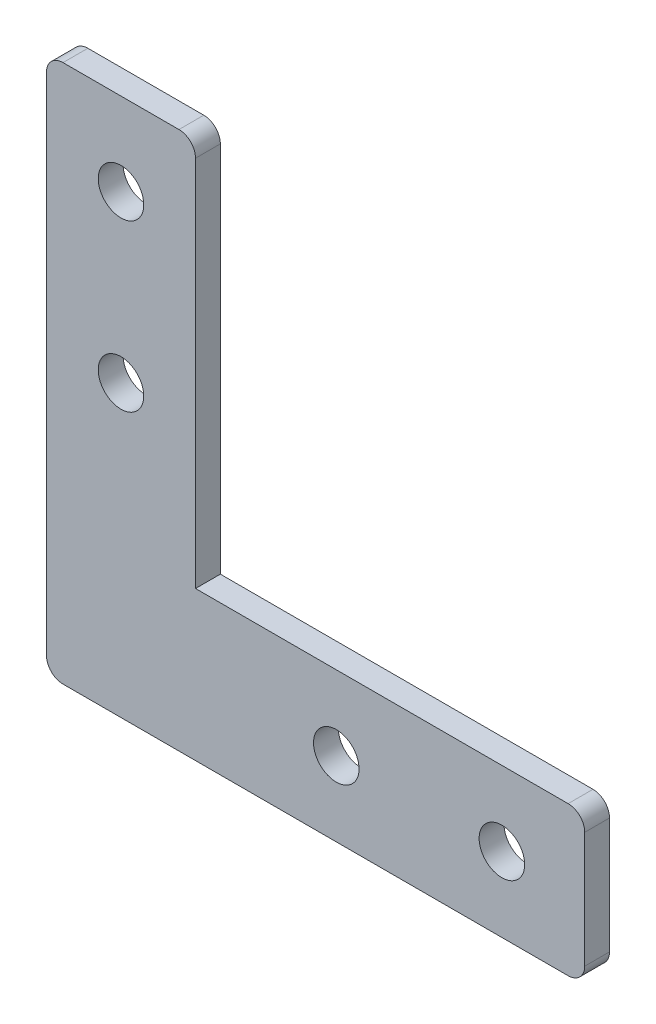
SolidWorks part; units mm, degrees
material "1023 Kohlenstoffstahlblech (SS)"
ref_plane "Ebene vorne" through (0, 0, 0) normal (0, 0, 1) x (1, 0, 0)
ref_plane "Ebene oben" through (0, 0, 0) normal (0, 1, 0) x (1, 0, 0)
ref_plane "Ebene rechts" through (0, 0, 0) normal (1, 0, 0) x (0, 0, -1)
sketch "Skizze1" plane through (0, 0, 0) normal (0, 0, 1) x (1, 0, 0)
  line L0 (0, 0) -> (0, 47)
  line L1 (0, 47) -> (-18, 47)
  line L2 (-18, 47) -> (-18, -18)
  line L3 (-18, -18) -> (47, -18)
  line L4 (47, -18) -> (47, 0)
  line L5 (47, 0) -> (0, 0)
  dimension "D1" = 18
  dimension "D2" = 65
extrude "Aufsatz-Linear austragen1" add sketch "Skizze1" along normal blind 3
hole_wizard "Durchgangsloch für M51" positions "Skizze2" profile "Skizze3" hole size "M5" standard "DIN" end condition through all
sketch "Skizze2" plane through (0, 0, 3) normal (0, 0, 1) x (1, 0, 0)
  line L0 (-9, 47) -> (-9, 37) construction
  line L1 (0, 47) -> (-18, 47) construction
  line L2 (-9, 37) -> (-9, 17) construction
  line L3 (-9, 17) -> (-9, -18) construction
  line L4 (-18, -18) -> (47, -18) construction
  line L7 (47, -9) -> (37, -9) construction
  line L8 (47, -18) -> (47, 0) construction
  line L9 (37, -9) -> (17, -9) construction
  line L10 (17, -9) -> (-18, -9) construction
  line L11 (-18, 47) -> (-18, -18) construction
  point P1 (-9, 37)
  point P4 (-9, 17)
  point P13 (37, -9)
  point P17 (17, -9)
  dimension "D1" = 35
  dimension "D2" = 20
sketch "Skizze3" plane through (17, -9, 3) normal (1, 0, 0) x (0, -1, 0)
  line L0 (0, 0) -> (0, 3)
  line L1 (0, 3) -> (2.75, 3)
  line L2 (2.75, 3) -> (2.75, 0)
  line L5 (2.75, 0) -> (0, 0)
  line L11 (0, -6.35) -> (0, 107.95) construction
  dimension "Bohrerdurchmesser" = 5.5
  dimension "Bohrungstiefe" = 3
fillet "Verrundung1" radius 2 5 edges at (47, 0, 1.5) (47, -18, 1.5) (-18, -18, 1.5) (-18, 47, 1.5) (0, 47, 1.5)
